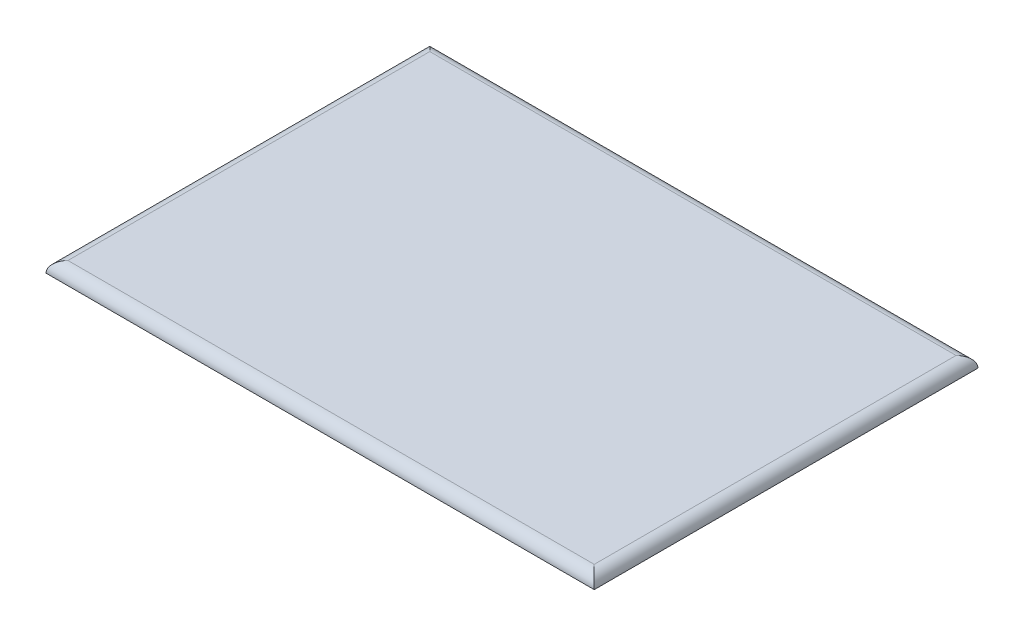
SolidWorks part; units mm, degrees
ref_plane "Front Plane" through (0, 0, 0) normal (0, 0, 1) x (1, 0, 0)
ref_plane "Top Plane" through (0, 0, 0) normal (0, 1, 0) x (1, 0, 0)
ref_plane "Right Plane" through (0, 0, 0) normal (1, 0, 0) x (0, 0, -1)
sketch "Sketch2" plane through (0, 0, 0) normal (0, 1, 0) x (1, 0, 0)
  line L1 (50, -35) -> (-50, -35)
  line L2 (50, -35) -> (50, 35)
  line L3 (50, 35) -> (-50, 35)
  line L4 (-50, -35) -> (-50, 35)
  line L5 (50, -35) -> (-50, 35) construction
  line L6 (50, 35) -> (-50, -35) construction
  point P0 (0, 0)
  dimension "D1" = 100
  dimension "D2" = 70
extrude "Boss-Extrude1" add sketch "Sketch2" along normal blind 2
fillet "Fillet1" radius 2 4 edges at (0, 2, -35) (50, 2, 0) (0, 2, 35) (-50, 2, 0)
